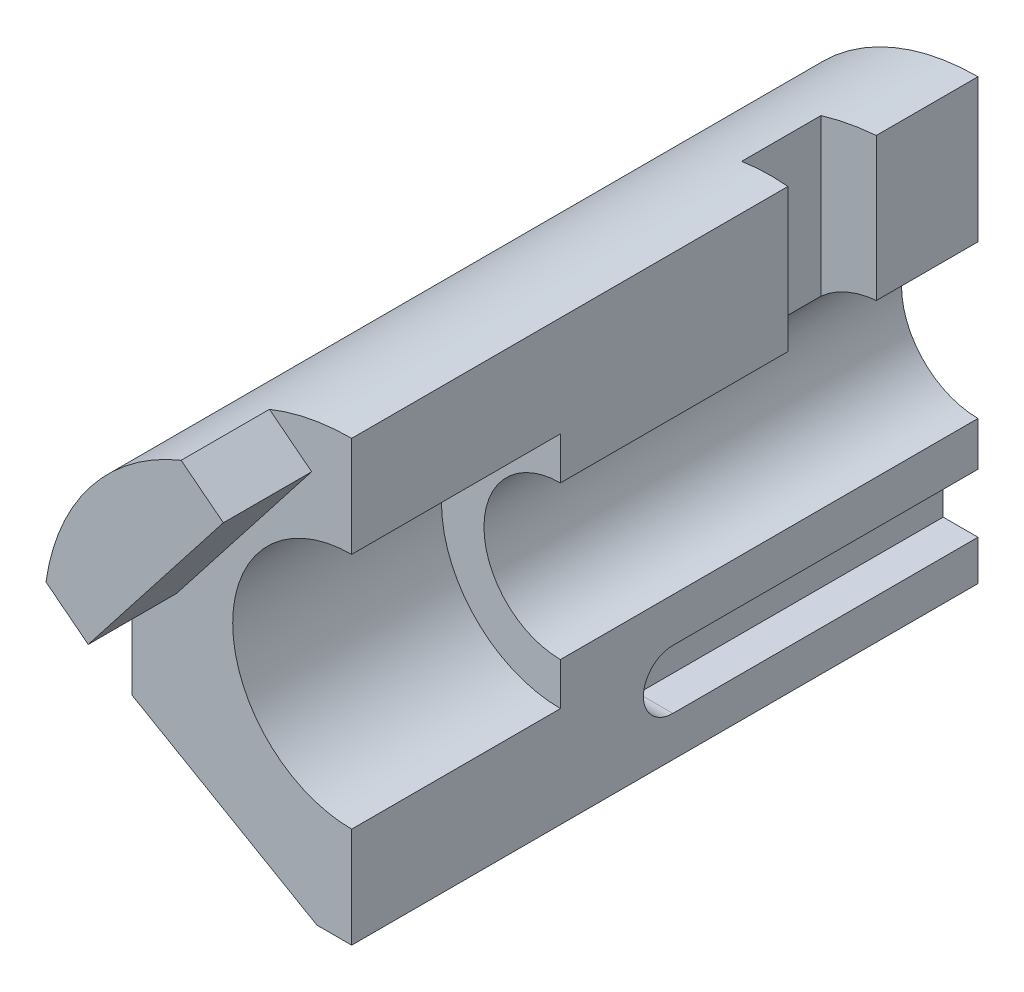
SolidWorks part; units mm, degrees
material "1060 Alloy"
ref_plane "Front Plane" through (0, 0, 0) normal (0, 0, 1) x (1, 0, 0)
ref_plane "Top Plane" through (0, 0, 0) normal (0, 1, 0) x (1, 0, 0)
ref_plane "Right Plane" through (0, 0, 0) normal (1, 0, 0) x (0, 0, -1)
sketch "Sketch1" plane through (0, 0, 0) normal (0, 0, 1) x (1, 0, 0)
  line L0 (0, 0) -> (-84.2231, 65.8023) construction
  line L1 (0, -28.575) -> (0, -82)
  line L2 (0, -82) -> (-13, -82)
  line L3 (-13, -82) -> (-82, -42.1628)
  line L4 (-82, -42.1628) -> (-82, 0)
  line L5 (0, 82) -> (0, 28.575)
  line L6 (-65.4307, -0.9097) -> (-14.9464, 63.7072)
  line L7 (-14.9464, 63.7072) -> (-30.7177, 76.0291)
  line L8 (-65.4307, -0.9097) -> (-81.202, 11.4122)
  arc A0 (0, 82) -> (-82, 0) centre (0, 0) ccw
  arc A1 (0, -28.575) -> (0, 28.575) centre (0, 0) cw
  arc A2 (0, 44.45) -> (0, -44.45) centre (0, 0) ccw
  point P7 (0, 44.6674)
  point P14 (-40.1885, 31.3987)
  point P16 (0, 0)
  dimension "D1" = 82
  dimension "D2" = 28.575
  dimension "D7" = 82
  dimension "D9" = 44.45
  dimension "D3" = 13
  dimension "D4" = 30
  dimension "D5" = 82
  dimension "D6" = 38
  dimension "D8" = 51
extrude "Boss-Extrude1" add sketch "Sketch1" against normal blind 234 contours A2 L0 L6 L8 A0 L4 L3 L2 L1 | A1 L0 A2 L1 | L0 A2 L5 A0 L7 L6 | L0 A1 L5 A2 | L6 L0 A0 L8 | L0 L6 L7 A0 region at (-26.8221, -13.082, 0) region at (-15.7059, 32.2019, 0) region at (-44.6477, -34.6549, 0) region at (-14.6676, 58.0975, 0) region at (-62.9432, 24.8715, 0) region at (-39.3601, 55.0565, 0)
extrude "Boss-Extrude2" add sketch "Sketch1<3>" along normal blind 33 contours L0 L6 L7 A0 | L6 L0 A0 L8 region at (-62.9432, 24.8715, 0) region at (-39.3601, 55.0565, 0)
sketch "Sketch1<3>" plane through (0, 0, 0) normal (0, 0, 1) x (1, 0, 0) same geometry as "Sketch1"
extrude "Cut-Extrude1" cut sketch "Sketch1<4>" against normal blind 78 contours L0 A1 L5 A2 | A1 L0 A2 L1 region at (-26.8221, -13.082, 0) region at (-15.7059, 32.2019, 0)
sketch "Sketch1<4>" plane through (0, 0, 0) normal (0, 0, 1) x (1, 0, 0) same geometry as "Sketch1"
sketch "Sketch2" plane through (0, 0, 0) normal (1, 0, 0) x (0, 0, -1)
  line L0 (120, -56) -> (234, -56) construction
  line L1 (234, -28.575) -> (234, -82) construction
  line L2 (120, -45) -> (234, -45)
  line L3 (120, -67) -> (234, -67)
  arc A0 (120, -45) -> (120, -67) centre (120, -56) ccw
  arc A1 (234, -67) -> (234, -45) centre (234, -56) ccw
  point P4 (177, -56)
  point P9 (176.7254, -62.4174)
  dimension "D2" = 11
  dimension "D1" = 26
  dimension "D3" = 114
extrude "Cut-Extrude2" cut sketch "Sketch2" against normal blind 13
ref_plane "Plane1" through (0, 82.055, 0) normal (0, 1, 0) x (1, 0, 0)
sketch "Sketch3" plane through (0, 82.055, 0) normal (0, 1, 0) x (1, 0, 0)
  line L0 (0, 234) -> (0, 0) construction
  line L1 (0, 163) -> (-19, 164.6623)
  line L3 (0, 196) -> (-19, 194.3377)
  line L4 (-19, 164.6623) -> (-19, 194.3377)
  line L5 (0, 163) -> (0, 196)
  line L6 (0, 234) -> (-82, 234) construction
  point P0 (-19, 188.4942)
  point P9 (0, 0)
  dimension "D1" = 38
  dimension "D2" = 33
  dimension "D3" = 19
  dimension "D4" = 5
  dimension "D5" = 5
extrude "Cut-Extrude3" cut sketch "Sketch3" against normal up to surface (60.7118 mm away) up to face at (-14.2875, 0, -156)
